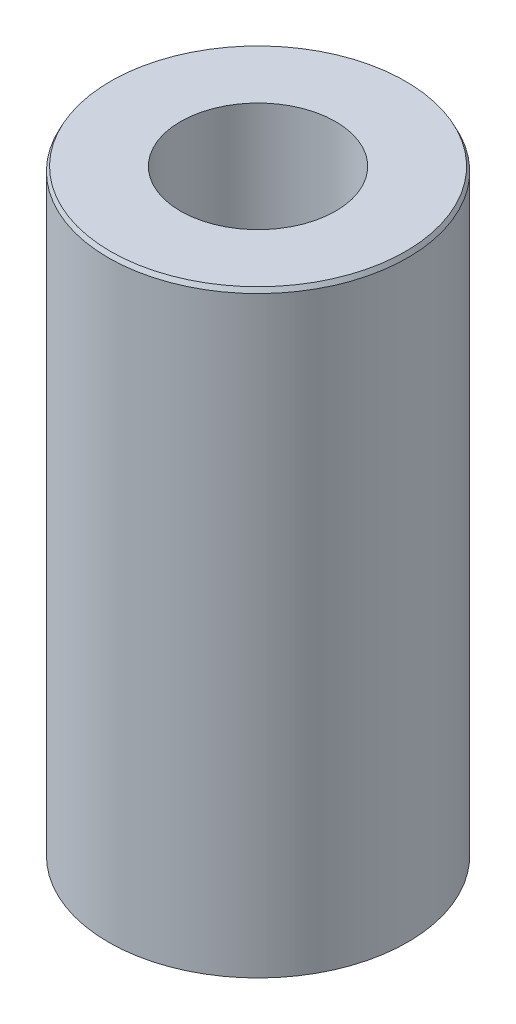
SolidWorks part; units mm, degrees
ref_plane "Front Plane" through (0, 0, 0) normal (0, 0, 1) x (1, 0, 0)
ref_plane "Top Plane" through (0, 0, 0) normal (0, 1, 0) x (1, 0, 0)
ref_plane "Right Plane" through (0, 0, 0) normal (1, 0, 0) x (0, 0, -1)
sketch "Sketch1" plane through (0, 0, 0) normal (0, 1, 0) x (1, 0, 0)
  circle A0 centre (0, 0) radius 17.5
  dimension "SHAFT_OD" = 35
extrude "Boss-Extrude1" add sketch "Sketch1" along normal blind 70.0691
sketch "Sketch2" plane through (0, 0, 0) normal (0, 1, 0) x (1, 0, 0)
  circle A0 centre (0, 0) radius 9.0718
  dimension "BORE_D" = 18.1436
extrude "Cut-Extrude1" cut sketch "Sketch2" along normal through all
chamfer "Chamfer1" distance 0.5111 angle 26.849 2 edges at (0, 70.0691, 17.5) (0, 0, 17.5) first distance on face at (0, 70.0691, 17.5) first distance on face at (0, 0, 9.0718)
